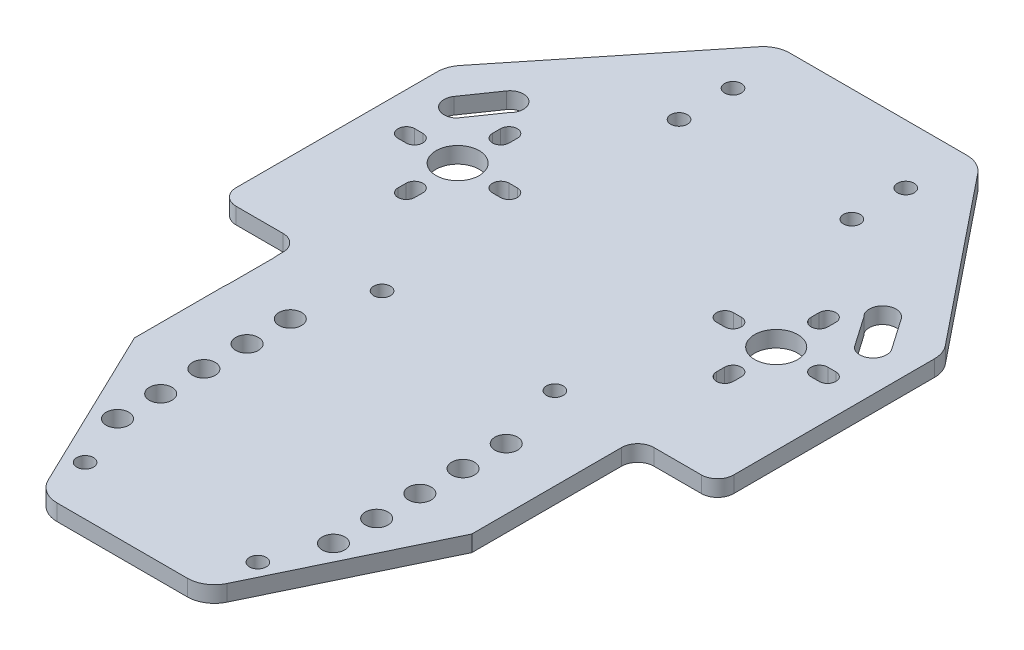
SolidWorks part; units mm, degrees
material "Thornel Mat VMA"
ref_plane "Front Plane" through (0, 0, 0) normal (0, 0, 1) x (1, 0, 0)
ref_plane "Top Plane" through (0, 0, 0) normal (0, 1, 0) x (1, 0, 0)
ref_plane "Right Plane" through (0, 0, 0) normal (1, 0, 0) x (0, 0, -1)
sketch "Sketch1" plane through (0, 0, 0) normal (0, 1, 0) x (1, 0, 0)
  line L0 (0, 0) -> (0, -27.5) construction
  line L1 (0, 0) -> (121.6069, 0) construction
  line L2 (37.5, 0) -> (39, 0) construction
  line L3 (37.5, 1.55) -> (39, 1.55)
  line L4 (37.5, -1.55) -> (39, -1.55)
  line L5 (29.5, -8) -> (29.5, -9.5) construction
  line L6 (31.05, -8) -> (31.05, -9.5)
  line L7 (27.95, -8) -> (27.95, -9.5)
  line L8 (21.5, 0) -> (20, 0) construction
  line L9 (21.5, -1.55) -> (20, -1.55)
  line L10 (21.5, 1.55) -> (20, 1.55)
  line L11 (29.5, 8) -> (29.5, 9.5) construction
  line L12 (27.95, 8) -> (27.95, 9.5)
  line L13 (31.05, 8) -> (31.05, 9.5)
  line L14 (20, -72.5) -> (20, -64.5) construction
  line L19 (-29.5, 8) -> (-29.5, 9.5) construction
  line L20 (-27.95, 8) -> (-27.95, 9.5)
  line L21 (-31.05, 8) -> (-31.05, 9.5)
  line L22 (-21.5, 0) -> (-20, 0) construction
  line L23 (-21.5, -1.55) -> (-20, -1.55)
  line L24 (-21.5, 1.55) -> (-20, 1.55)
  line L25 (-29.5, -8) -> (-29.5, -9.5) construction
  line L26 (-31.05, -8) -> (-31.05, -9.5)
  line L27 (-27.95, -8) -> (-27.95, -9.5)
  line L28 (-37.5, 0) -> (-39, 0) construction
  line L29 (-37.5, 1.55) -> (-39, 1.55)
  line L30 (-37.5, -1.55) -> (-39, -1.55)
  line L31 (-31.3246, -40.5321) -> (-31.3246, -32.4375)
  line L34 (-38.4806, -33.6183) -> (-38.4806, -40.5321)
  line L35 (31.3246, -40.5321) -> (31.3246, -32.4375)
  line L36 (38.4806, -33.6183) -> (38.4806, -40.5321)
  line L37 (-36.8266, 7.1221) -> (-32.8384, 12.8748)
  line L38 (29.5, 0) -> (50.8627, -25.4591) construction
  line L41 (46, 48.4159) -> (-46, 48.4159)
  line L44 (46, 48.4159) -> (46.1488, -91.633)
  line L47 (46.1488, -91.633) -> (-46.1487, -91.584)
  line L50 (-46, 48.4159) -> (-46.1487, -91.584)
  line L53 (-36.5402, 16.1211) -> (-40.5285, 10.3684)
  line L59 (-959, -57) -> (49041, -57) construction
  line L63 (36.8266, 7.1221) -> (32.8384, 12.8748)
  line L64 (36.5402, 16.1211) -> (40.5285, 10.3684)
  circle A0 centre (29.5, 0) radius 4
  arc A1 (37.5, 1.55) -> (37.5, -1.55) centre (37.5, 0) ccw
  arc A2 (39, -1.55) -> (39, 1.55) centre (39, 0) ccw
  arc A3 (31.05, -8) -> (27.95, -8) centre (29.5, -8) ccw
  arc A4 (27.95, -9.5) -> (31.05, -9.5) centre (29.5, -9.5) ccw
  arc A5 (21.5, -1.55) -> (21.5, 1.55) centre (21.5, 0) ccw
  arc A6 (20, 1.55) -> (20, -1.55) centre (20, 0) ccw
  arc A7 (27.95, 8) -> (31.05, 8) centre (29.5, 8) ccw
  arc A8 (31.05, 9.5) -> (27.95, 9.5) centre (29.5, 9.5) ccw
  circle A13 centre (-29.5, 0) radius 4
  arc A14 (-27.95, 8) -> (-31.05, 8) centre (-29.5, 8) cw
  arc A15 (-31.05, 9.5) -> (-27.95, 9.5) centre (-29.5, 9.5) cw
  arc A16 (-21.5, -1.55) -> (-21.5, 1.55) centre (-21.5, 0) cw
  arc A17 (-20, 1.55) -> (-20, -1.55) centre (-20, 0) cw
  arc A18 (-31.05, -8) -> (-27.95, -8) centre (-29.5, -8) cw
  arc A19 (-27.95, -9.5) -> (-31.05, -9.5) centre (-29.5, -9.5) cw
  arc A20 (-37.5, 1.55) -> (-37.5, -1.55) centre (-37.5, 0) cw
  arc A21 (-39, -1.55) -> (-39, 1.55) centre (-39, 0) cw
  circle A22 centre (16, 27.5) radius 1.55
  circle A23 centre (16, -27.5) radius 1.55
  circle A24 centre (-16, -27.5) radius 1.55
  circle A25 centre (-16, 27.5) radius 1.55
  circle A76 centre (-16, 37.5) radius 1.55
  circle A77 centre (16, 37.5) radius 1.55
  circle A78 centre (20, -72.5) radius 2.1
  circle A79 centre (-20, -72.5) radius 2.1
  circle A83 centre (-20, -40.5) radius 2.1
  circle A84 centre (20, -40.5) radius 2.1
  circle A85 centre (20, -64.5) radius 2.1
  circle A86 centre (-20, -64.5) radius 2.1
  circle A87 centre (20, -56.5) radius 2.1
  circle A88 centre (-20, -56.5) radius 2.1
  circle A89 centre (20, -48.5) radius 2.1
  circle A90 centre (-20, -48.5) radius 2.1
  circle A91 centre (-16, -82.5) radius 1.55
  circle A92 centre (16, -82.5) radius 1.55
  arc A93 (-38.4806, -40.5321) -> (-31.3246, -40.5321) centre (-34.9026, -40.5321) ccw
  arc A94 (-31.3246, -32.4375) -> (-38.4806, -33.6183) centre (-35, -32.4375) ccw
  arc A95 (38.4806, -40.5321) -> (31.3246, -40.5321) centre (34.9026, -40.5321) cw
  arc A96 (31.3246, -32.4375) -> (38.4806, -33.6183) centre (35, -32.4375) cw
  arc A103 (-40.5285, 10.3684) -> (-36.8266, 7.1221) centre (-38.4922, 8.9566) ccw
  arc A106 (-36.5402, 16.1211) -> (-32.8384, 12.8748) centre (-34.5039, 14.7093) cw
  arc A107 (36.5402, 16.1211) -> (32.8384, 12.8748) centre (34.5039, 14.7093) ccw
  arc A108 (40.5285, 10.3684) -> (36.8266, 7.1221) centre (38.4922, 8.9566) cw
  point P8 (38.25, 0)
  point P18 (29.5, -8.75)
  point P25 (20.75, 0)
  point P32 (29.5, 8.75)
  point P37 (29.5, 0)
  point P51 (0, 32.5)
  point P55 (-29.5, 8.75)
  point P62 (-20.75, 0)
  point P69 (-29.5, -8.75)
  point P76 (-38.25, 0)
  dimension "D1" = 8
  dimension "D2" = 1.55
  dimension "D4" = 8
  dimension "D5" = 4
  dimension "D6" = 92
  dimension "D7" = 140
  dimension "D8" = 2
  dimension "D9" = 59
  dimension "D10" = 3.1
  dimension "D11" = 40
  dimension "D12" = 27.5
  dimension "D13" = 8
  dimension "D15" = 7
  dimension "D27" = 4.2
  dimension "D28" = 100
  dimension "D3" = 1.5
  dimension "D14" = 35
  dimension "D16" = 7
  dimension "D23" = 50
extrude "Boss-Extrude1" [suppressed] add sketch "Sketch1" along normal blind 3
sketch "草图7" [suppressed] plane through (0, 0, 0) normal (0, 1, 0) x (1, 0, 0)
  line L0 (0, 0) -> (0, -97.058) construction
  line L1 (-27.95, -9.5) -> (-27.95, -8) construction
  line L2 (22.2054, 32.5) -> (-23.2593, 32.5) construction
  line L3 (-31.05, -8) -> (-31.05, -9.5) construction
  line L4 (-37.5, 1.55) -> (-39, 1.55)
  line L5 (-39, -1.55) -> (-37.5, -1.55)
  line L6 (-37.5, 1.55) -> (-39, 1.55)
  line L7 (-39, -1.55) -> (-37.5, -1.55)
  line L8 (-27.95, 8) -> (-27.95, 9.5)
  line L9 (-31.05, 9.5) -> (-31.05, 8)
  line L10 (-27.95, 8) -> (-27.95, 9.5)
  line L11 (-31.05, 9.5) -> (-31.05, 8)
  line L12 (-21.5, -1.55) -> (-20, -1.55)
  line L13 (-20, 1.55) -> (-21.5, 1.55)
  line L14 (-21.5, -1.55) -> (-20, -1.55)
  line L15 (-20, 1.55) -> (-21.5, 1.55)
  line L16 (-27.95, -9.5) -> (-27.95, -8)
  line L17 (-31.05, -8) -> (-31.05, -9.5)
  line L20 (37.5, -1.55) -> (39, -1.55)
  line L21 (39, 1.55) -> (37.5, 1.55)
  line L22 (37.5, -1.55) -> (39, -1.55)
  line L23 (39, 1.55) -> (37.5, 1.55)
  line L24 (27.95, -8) -> (27.95, -9.5)
  line L25 (31.05, -9.5) -> (31.05, -8)
  line L26 (27.95, -8) -> (27.95, -9.5)
  line L27 (31.05, -9.5) -> (31.05, -8)
  line L28 (21.5, 1.55) -> (20, 1.55)
  line L29 (20, -1.55) -> (21.5, -1.55)
  line L30 (21.5, 1.55) -> (20, 1.55)
  line L31 (20, -1.55) -> (21.5, -1.55)
  line L32 (31.05, 8) -> (31.05, 9.5)
  line L33 (27.95, 9.5) -> (27.95, 8)
  line L34 (31.05, 8) -> (31.05, 9.5)
  line L35 (27.95, 9.5) -> (27.95, 8)
  circle A0 centre (29.5, 0) radius 4 construction
  circle A1 centre (29.5, 0) radius 4
  circle A3 centre (-20, -72.5) radius 1.55
  circle A4 centre (-29.5, 0) radius 4
  circle A5 centre (-29.5, 0) radius 4
  circle A6 centre (16, 27.5) radius 1.55
  circle A7 centre (16, 27.5) radius 1.55
  circle A8 centre (-16, 27.5) radius 1.55
  circle A9 centre (-16, 27.5) radius 1.55
  circle A12 centre (16, 37.5) radius 1.55
  circle A13 centre (-16, 37.5) radius 1.55
  circle A14 centre (-16, -27.5) radius 1.55
  circle A15 centre (20, -72.5) radius 1.55
  arc A16 (-31.05, -9.5) -> (-27.95, -9.5) centre (-29.5, -9.5) ccw construction
  arc A18 (-37.5, -1.55) -> (-37.5, 1.55) centre (-37.5, 0) ccw
  arc A19 (-39, 1.55) -> (-39, -1.55) centre (-39, 0) ccw
  arc A20 (-37.5, -1.55) -> (-37.5, 1.55) centre (-37.5, 0) ccw
  arc A21 (-39, 1.55) -> (-39, -1.55) centre (-39, 0) ccw
  arc A23 (-27.95, -8) -> (-31.05, -8) centre (-29.5, -8) ccw construction
  arc A24 (-31.05, 8) -> (-27.95, 8) centre (-29.5, 8) ccw
  arc A25 (-27.95, 9.5) -> (-31.05, 9.5) centre (-29.5, 9.5) ccw
  arc A26 (-31.05, 8) -> (-27.95, 8) centre (-29.5, 8) ccw
  arc A27 (-27.95, 9.5) -> (-31.05, 9.5) centre (-29.5, 9.5) ccw
  arc A28 (-21.5, 1.55) -> (-21.5, -1.55) centre (-21.5, 0) ccw
  arc A29 (-20, -1.55) -> (-20, 1.55) centre (-20, 0) ccw
  arc A30 (-21.5, 1.55) -> (-21.5, -1.55) centre (-21.5, 0) ccw
  arc A31 (-20, -1.55) -> (-20, 1.55) centre (-20, 0) ccw
  arc A32 (-31.05, -9.5) -> (-27.95, -9.5) centre (-29.5, -9.5) ccw
  arc A33 (-27.95, -8) -> (-31.05, -8) centre (-29.5, -8) ccw
  circle A34 centre (16, -27.5) radius 1.55
  arc A36 (37.5, 1.55) -> (37.5, -1.55) centre (37.5, 0) ccw
  arc A37 (39, -1.55) -> (39, 1.55) centre (39, 0) ccw
  arc A38 (37.5, 1.55) -> (37.5, -1.55) centre (37.5, 0) ccw
  arc A39 (39, -1.55) -> (39, 1.55) centre (39, 0) ccw
  arc A40 (31.05, -8) -> (27.95, -8) centre (29.5, -8) ccw
  arc A41 (27.95, -9.5) -> (31.05, -9.5) centre (29.5, -9.5) ccw
  arc A42 (31.05, -8) -> (27.95, -8) centre (29.5, -8) ccw
  arc A43 (27.95, -9.5) -> (31.05, -9.5) centre (29.5, -9.5) ccw
  arc A44 (21.5, -1.55) -> (21.5, 1.55) centre (21.5, 0) ccw
  arc A45 (20, 1.55) -> (20, -1.55) centre (20, 0) ccw
  arc A46 (21.5, -1.55) -> (21.5, 1.55) centre (21.5, 0) ccw
  arc A47 (20, 1.55) -> (20, -1.55) centre (20, 0) ccw
  arc A48 (27.95, 8) -> (31.05, 8) centre (29.5, 8) ccw
  arc A49 (31.05, 9.5) -> (27.95, 9.5) centre (29.5, 9.5) ccw
  arc A50 (27.95, 8) -> (31.05, 8) centre (29.5, 8) ccw
  arc A51 (31.05, 9.5) -> (27.95, 9.5) centre (29.5, 9.5) ccw
  dimension "D4" = 3.1
  dimension "D6" = 20
  dimension "D7" = 5
  dimension "D9" = 3.1
  dimension "D16" = 32
  dimension "D17" = 55
  dimension "D5" = 100
  dimension "D8" = 0
  dimension "D1" = 0
  dimension "D2" = 0
  dimension "D3" = 0
  dimension "D10" = 0
  dimension "D11" = 0
  dimension "D12" = 0
  dimension "D13" = 0
  dimension "D14" = 0
  dimension "D15" = 0
extrude "凸台-拉伸1" add sketch "Sketch1<2>" along normal blind 3 contours L41 L50 L47 L44 A79 A78 A23 A22 A0 A2 L4 A1 L3 A4 L7 A3 L6 A6 L10 A5 L9 A8 L13 A7 L12 A13 L21 A15 L20 A14 L24 A17 L23 A16 region at (0.0029, 0, 21.6938)
sketch "Sketch1<2>" plane through (0, 0, 0) normal (0, 1, 0) x (1, 0, 0) same geometry as "Sketch1"
sketch "草图8" plane through (0, 0, 0) normal (0, 1, 0) x (1, 0, 0)
  line L0 (-11.1069, -100.1389) -> (-60.5812, 2.6993)
  line L1 (-60.5812, 2.6993) -> (-60.5812, -100.1389)
  line L2 (-60.5812, -100.1389) -> (-11.1069, -100.1389)
  line L3 (0, -21.5721) -> (0, 8.1084) construction
  line L4 (60.5812, -100.1389) -> (11.1069, -100.1389)
  line L5 (60.5812, 2.6993) -> (60.5812, -100.1389)
  line L6 (11.1069, -100.1389) -> (60.5812, 2.6993)
  line L7 (-55.5478, 2.6866) -> (-14.4304, 53.8253)
  line L8 (-14.4304, 53.8253) -> (-55.5478, 53.8253)
  line L9 (-55.5478, 53.8253) -> (-55.5478, 2.6866)
  line L10 (55.5478, 53.8253) -> (55.5478, 2.6866)
  line L11 (14.4304, 53.8253) -> (55.5478, 53.8253)
  line L12 (55.5478, 2.6866) -> (14.4304, 53.8253)
  line L13 (-46.0806, -27.4419) -> (-31.3889, -27.4419)
  line L14 (-46, 48.4159) -> (-46.1487, -91.584) construction
  line L15 (-31.3889, -27.4419) -> (-31.3889, -57.9803)
  line L16 (46.0806, -27.4419) -> (31.2972, -27.4419)
  line L17 (31.2972, -27.4419) -> (31.2972, -58.171)
  line L18 (-31.3246, -40.5321) -> (-31.3246, -32.4375) construction
  line L19 (-31.3246, -40.5321) -> (-31.3246, -32.4375)
extrude "切除-拉伸1" cut sketch "草图8" along normal through all contours L1 L2 L0 | L8 L9 L7 | L12 L10 L11 | L6 L4 L5 | L16 L17 L6 | L15 L13 L0 region at (-44.0897, 0, 65.8595) region at (-36.2861, 0, 37.6214) region at (44.0897, 0, 65.8595) region at (36.225, 0, 37.6849) region at (-41.842, 0, -36.779) region at (41.842, 0, -36.779)
fillet "圆角1" radius 5 6 edges at (-15.2146, 1.5, 91.6005) (15.2069, 1.5, 91.6166) (46.036, 1.5, -14.5166) (18.7797, 1.5, -48.4159) (-18.7797, 1.5, -48.4159) (-46.036, 1.5, -14.5166)
fillet "圆角2" radius 3 4 edges at (-46.0806, 1.5, 27.4419) (-31.3889, 1.5, 27.4419) (31.2972, 1.5, 27.4419) (46.0806, 1.5, 27.4419)
